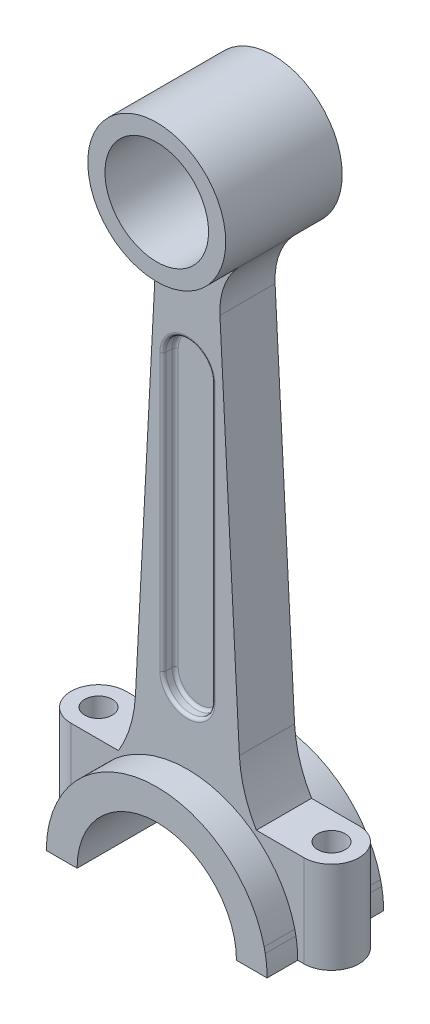
SolidWorks part; units mm, degrees
ref_plane "Front Plane" through (0, 0, 0) normal (0, 0, 1) x (1, 0, 0)
ref_plane "Top Plane" through (0, 0, 0) normal (0, 1, 0) x (1, 0, 0)
ref_plane "Right Plane" through (0, 0, 0) normal (1, 0, 0) x (0, 0, -1)
sketch "Sketch1" plane through (0, 0, 0) normal (0, 0, 1) x (1, 0, 0)
  line L0 (0, 42.4069) -> (0, -201.2) construction
  line L1 (-55.4216, 0) -> (61.3997, 0) construction
  line L2 (-35.389, -194.5958) -> (-35.026, -192.8827)
  line L3 (35.389, -194.5958) -> (35.026, -192.8827)
  line L4 (-10, -20.1556) -> (-17.8497, -169.9368)
  line L5 (10, -20.1556) -> (17.8497, -169.9368)
  line L6 (-36, -201.2) -> (-26, -201.2)
  line L7 (26, -201.2) -> (36, -201.2)
  circle A0 centre (0, 0) radius 22.5
  circle A1 centre (0, 0) radius 16.9
  arc A2 (36, -201.2) -> (-36, -201.2) centre (0, -201.2) ccw
  arc A3 (26, -201.2) -> (-26, -201.2) centre (0, -201.2) ccw
  dimension "D1" = 45
  dimension "D2" = 33.8
  dimension "D3" = 72
  dimension "D4" = 52
  dimension "D5" = 201.2
  dimension "D6" = 20
  dimension "D7" = 6
extrude "Boss-Extrude4" add sketch "Sketch1" along normal mid plane 38 contours A0 A1 | L3 A2 L2 A3 region at (-34.42, -193.9061, 0) region at (-11.5231, 18.5805, 0)
extrude "Boss-Extrude5" add sketch "Sketch1<7>" along normal mid plane 18 contours A2 L5 A0 L4 region at (0, -100.8455, 0)
sketch "Sketch1<7>" plane through (0, 0, 0) normal (0, 0, 1) x (1, 0, 0) same geometry as "Sketch1"
sketch "Sketch2" plane through (0, 0, 9) normal (0, 0, 1) x (1, 0, 0)
  line L0 (0, 0) -> (0, -203.0188) construction
  line L1 (0, -51.9322) -> (0, -141.9322) construction
  line L2 (8, -51.9322) -> (8, -141.9322)
  line L3 (-8, -51.9322) -> (-8, -141.9322)
  arc A0 (8, -51.9322) -> (-8, -51.9322) centre (0, -51.9322) ccw
  arc A1 (-8, -141.9322) -> (8, -141.9322) centre (0, -141.9322) ccw
  point P5 (0, -96.9322)
  dimension "D2" = 8
  dimension "D1" = 90
extrude "Cut-Extrude1" cut sketch "Sketch2" against normal blind 4
mirror "Mirror1" about plane through (0, 0, 0) normal (0, 0, 1) of "Cut-Extrude1"
fillet "Fillet1" radius 1 16 edges at (0, -43.9322, -9) (8, -96.9322, -9) (0, -149.9322, -9) (0, -43.9322, -5) (8, -96.9322, -5) (0, -149.9322, -5) (0, -43.9322, 5) (8, -96.9322, 5) (0, -149.9322, 5) (0, -43.9322, 9) (8, -96.9322, 9) (0, -149.9322, 9) (-8, -96.9322, -9) (-8, -96.9322, -5) (-8, -96.9322, 5) (-8, -96.9322, 9)
fillet "Fillet2" radius 22.5 2 edges at (-10, -20.1556, 0) (10, -20.1556, 0)
fillet "Fillet3" radius 40 2 edges at (-17.8497, -169.9368, 0) (17.8497, -169.9368, 0)
ref_plane "Plane1" through (0, -171.2, 0) normal (0, 1, 0) x (1, 0, 0)
sketch "Sketch3" plane through (0, -171.2, 0) normal (0, 1, 0) x (1, 0, 0)
  line L0 (-38, 0) -> (38, 0) construction
  line L1 (-38, 9) -> (38, 9)
  line L2 (-38, -9) -> (38, -9)
  arc A0 (-38, 9) -> (-38, -9) centre (-38, 0) ccw
  arc A1 (38, -9) -> (38, 9) centre (38, 0) ccw
  point P2 (0, 0)
  dimension "D2" = 9
  dimension "D1" = 76
extrude "Boss-Extrude6" add sketch "Sketch3" against normal up to surface (30 mm away) up to face at (-31, -201.2, 0)
sketch "Sketch6" plane through (0, 0, 9) normal (0, 0, 1) x (1, 0, 0)
  line L0 (26, -201.2) -> (-26, -201.2) construction
  circle A0 centre (0, -201.2) radius 26
extrude "Cut-Extrude2" cut sketch "Sketch6" against normal through all both and the other way through all
sketch "Sketch7" plane through (0, -171.2, 0) normal (0, 1, 0) x (1, 0, 0)
  circle A0 centre (-38, 0) radius 4.5
  circle A1 centre (38, 0) radius 4.5
  dimension "D1" = 9
  dimension "D2" = 9
extrude "Cut-Extrude3" cut sketch "Sketch7" against normal through all both
